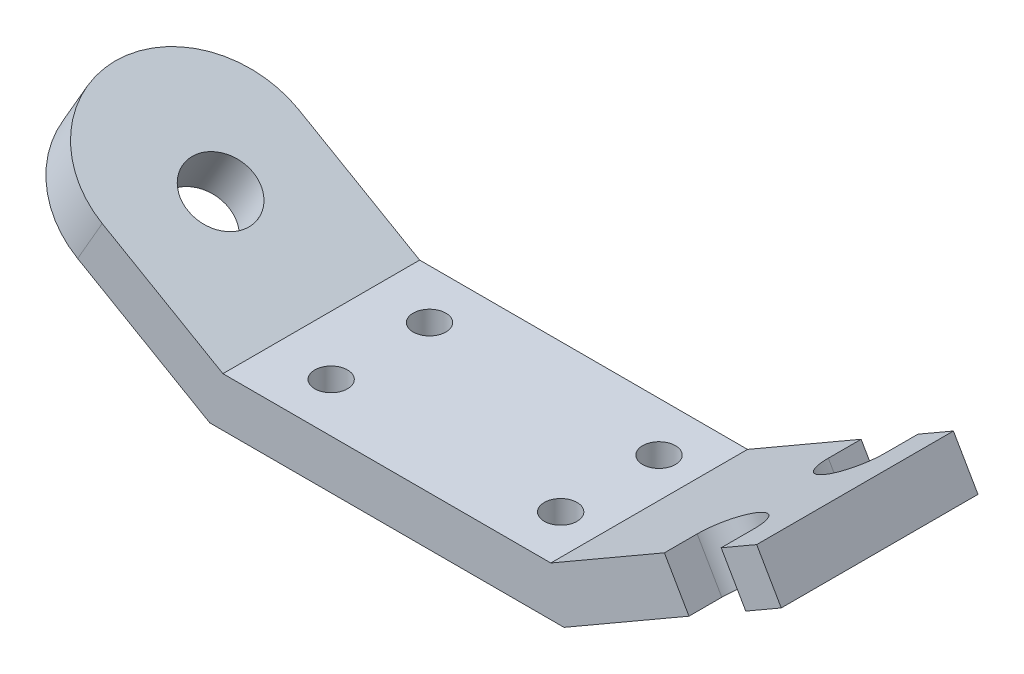
SolidWorks part; units mm, degrees
ref_plane "前基準面" through (0, 0, 0) normal (0, 0, 1) x (1, 0, 0)
ref_plane "上基準面" through (0, 0, 0) normal (0, 1, 0) x (1, 0, 0)
ref_plane "右基準面" through (0, 0, 0) normal (1, 0, 0) x (0, 0, -1)
sketch "草圖1" plane through (0, 0, 0) normal (0, 0, 1) x (1, 0, 0)
  line L0 (0, 0) -> (-50.2295, 29)
  line L1 (0, 0) -> (80, 0)
  line L2 (80, 0) -> (130.2295, 29)
  dimension "D1" = 30
  dimension "D2" = 30
  dimension "D3" = 58
  dimension "D4" = 58
  dimension "D5" = 80
extrude "伸長-薄件1" add sketch "草圖1" along normal mid plane 48 thin thin type one direction wall 12
fillet "圓角1" 2 edges at (-53.2295, 23.8038, 24) (-53.2295, 23.8038, -24) type full round first side face at (40, 8.9019, 24) second side face at (40, 8.9019, -24) middle face at (-53.2295, 23.8038, 0)
sketch "草圖3" plane through (0, 0, 0) normal (0.5, 0.866, 0) x (0.866, -0.5, 0)
  circle A0 centre (-28.3673, 0) radius 8
  dimension "D1" = 16
extrude "除料-伸長2" cut sketch "草圖3" against normal through all
sketch "草圖4" plane through (0, 0, 0) normal (0, 1, 0) x (1, 0, 0)
  line L0 (0, 0) -> (50.6989, 0) construction
  circle A0 centre (14.4066, -12) radius 4
  circle A1 centre (70.4066, -12) radius 4
  circle A2 centre (70.4066, 12) radius 4
  circle A3 centre (14.4066, 12) radius 4
  dimension "D1" = 8
  dimension "D2" = 8
  dimension "D3" = 56
  dimension "D4" = 24
extrude "除料-伸長3" cut sketch "草圖4" against normal through all
sketch "草圖5" plane through (20, -34.641, 0) normal (-0.5, 0.866, 0) x (0.866, 0.5, 0)
  line L0 (101.282, -24) -> (101.282, -16)
  line L1 (69.282, -24) -> (127.282, -24) construction
  line L2 (117.282, -16) -> (117.282, -24)
  line L3 (117.282, -24) -> (101.282, -24)
  line L4 (67.4541, 0) -> (129.2728, 0) construction
  line L5 (117.282, 24) -> (101.282, 24)
  line L6 (101.282, 24) -> (101.282, 16)
  line L7 (117.282, 16) -> (117.282, 24)
  line L8 (69.282, -24) -> (69.282, 24) construction
  arc A0 (101.282, -16) -> (117.282, -16) centre (109.282, -16) cw
  arc A1 (101.282, 16) -> (117.282, 16) centre (109.282, 16) ccw
  dimension "D1" = 32
  dimension "D2" = 16
  dimension "D3" = 40
extrude "除料-伸長4" cut sketch "草圖5" against normal through all
